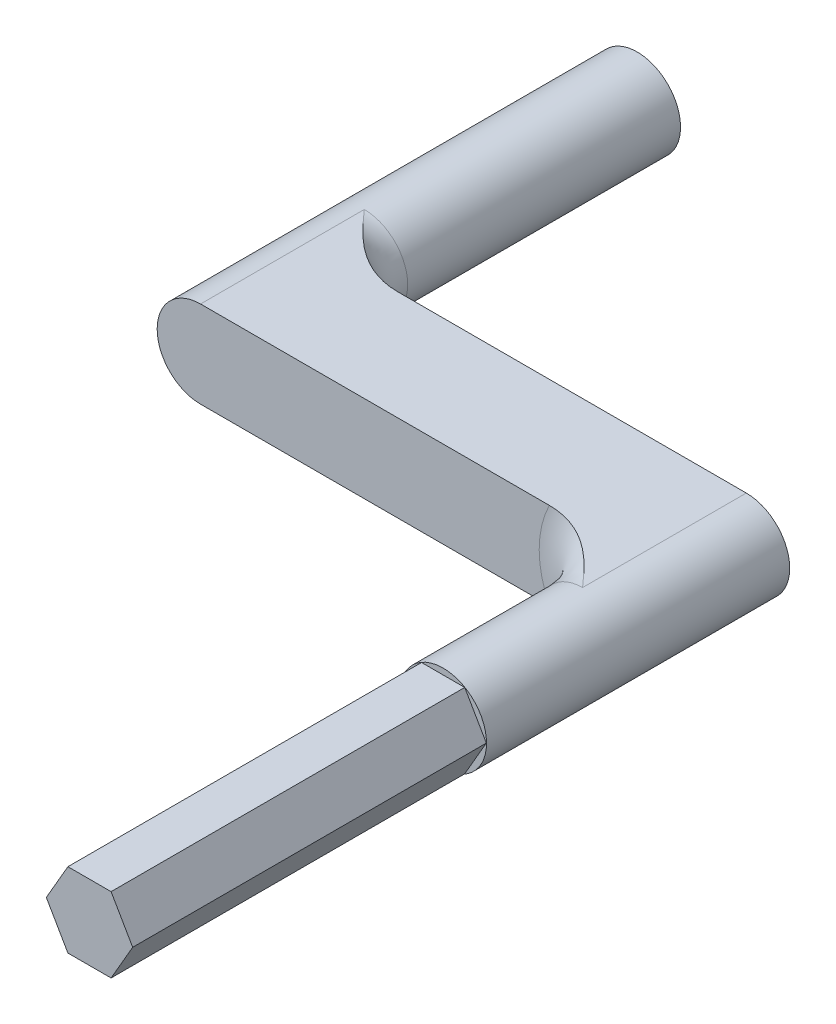
SolidWorks part; units mm, degrees
material "PETG"
ref_plane "Front Plane" through (0, 0, 0) normal (0, 0, 1) x (1, 0, 0)
ref_plane "Top Plane" through (0, 0, 0) normal (0, 1, 0) x (1, 0, 0)
ref_plane "Right Plane" through (0, 0, 0) normal (1, 0, 0) x (0, 0, -1)
sketch "Sketch1" plane through (0, 0, 0) normal (0, 0, 1) x (1, 0, 0)
  circle A0 centre (0, 0) radius 3.975
  dimension "Shaft Dia" = 7.95
extrude "Boss-Extrude1" add sketch "Sketch1" along normal blind 17.775
sketch "Sketch2" plane through (0, 0, 17.775) normal (0, 0, 1) x (1, 0, 0)
  line L1 (4, 0) -> (2, 3.4641) construction
  line L2 (2, 3.4641) -> (-2, 3.4641) construction
  line L3 (-2, 3.4641) -> (-4, 0) construction
  line L4 (-4, 0) -> (-2, -3.4641) construction
  line L5 (-2, -3.4641) -> (2, -3.4641) construction
  line L6 (2, -3.4641) -> (4, 0) construction
  line L7 (3.9567, 0) -> (1.9783, 3.4266)
  line L8 (1.9783, 3.4266) -> (-1.9783, 3.4266)
  line L9 (-1.9783, 3.4266) -> (-3.9567, 0)
  line L10 (-3.9567, 0) -> (-1.9783, -3.4266)
  line L11 (-1.9783, -3.4266) -> (1.9783, -3.4266)
  line L12 (1.9783, -3.4266) -> (3.9567, 0)
  circle A0 centre (0, 0) radius 3.4641 construction
  circle A1 centre (0, 0) radius 3.4266 construction
  dimension "Hex Circumscribed Nominal Dia" = 8
  dimension "Hex Flat To Flat Offset" = 0.0375
extrude "Boss-Extrude2" add sketch "Sketch2" along normal blind 32.4
sketch "Sketch3" plane through (0, 0, 0) normal (0, 0, -1) x (-1, 0, 0)
  line L0 (0, 0) -> (40, 0) construction
  line L1 (0, 3.975) -> (40, 3.975)
  line L2 (0, -3.975) -> (40, -3.975)
  arc A0 (0, 3.975) -> (0, -3.975) centre (0, 0) ccw
  arc A1 (40, -3.975) -> (40, 3.975) centre (40, 0) ccw
  circle A2 centre (0, 0) radius 3.975 construction
  point P3 (20, 0)
  dimension "D1" = 40
extrude "Boss-Extrude3" add sketch "Sketch3" along normal blind 10
fillet "Fillet1" radius 5 1 edges at (-3.975, 0, 0)
sketch "Sketch4" plane through (0, 0, -10) normal (0, 0, -1) x (-1, 0, 0)
  circle A0 centre (40, 0) radius 3.975
extrude "Boss-Extrude4" add sketch "Sketch4" along normal blind 30
fillet "Fillet2" radius 5 1 edges at (-36.025, 0, -10)
equation "\"tol_dia_id_intfc\" = 0.0500mm ' For hole diameters - Interference fit"
equation "\"tol_dia_id_slip\"  = 0.0750mm ' For hole diameters - Slip fit"
equation "\"tol_dia_id_clear\" = 0.1000mm ' For hole diameters - Clearance fit"
equation "\"tol_dia_od_intfc\" = 0.0500mm ' For shaft diameters - Interference fit"
equation "\"tol_dia_od_slip\"  = 0.0750mm ' For shaft diameters - Slip fit"
equation "\"tol_dia_od_clear\" = 0.1000mm ' For shaft diameters - Clearance fit"
equation "\"tol_general_intfc\"= 0.0250mm ' For general parts (Horiz) - Interference fit"
equation "\"tol_general_slip\" = 0.0375mm ' For general parts (Horiz) - Slip fit"
equation "\"tol_general_clear\"= 0.0500mm ' For general parts (Horiz) - Clearance fit"
equation "\"tol_layer_intfc\"  = 0.0250mm ' For all parts (Vert) - Interference fit"
equation "\"tol_layer_slip\"   = 0.0375mm ' For all parts (Vert) - Slip fit"
equation "\"tol_layer_clear\"  = 0.0500mm ' For all parts (Vert) - Clearance fit"
equation "\"tol_corner_rad\"   = 0.100mm ' For corners that fit into other parts"
equation "\"Shaft Dia@Sketch1\" = \"nominal_dia\" - \"tol_dia_od_intfc\""
equation "\"nominal_dia\"= 8.00mm"
equation "\"Hex Circumscribed Nominal Dia@Sketch2\" = \"nominal_dia\""
equation "\"Hex Flat To Flat Offset@Sketch2\"= \"tol_general_slip\""
equation "\"D1@Boss-Extrude2\"=32.50mm-\"tol_layer_clear\"*2"
